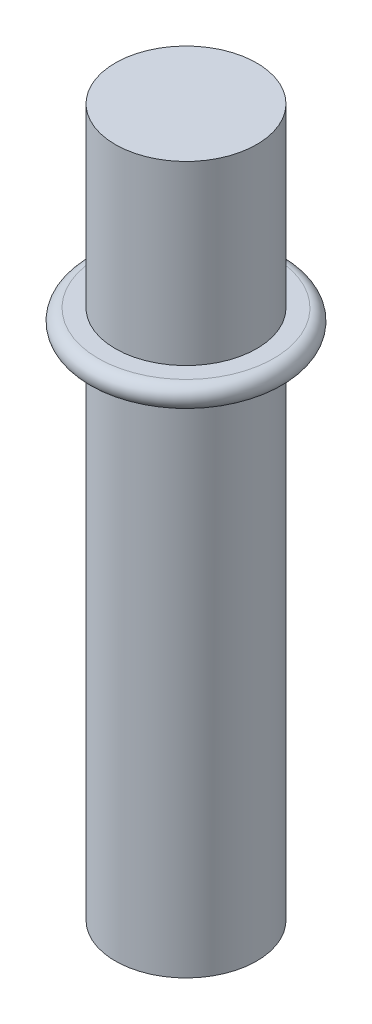
SolidWorks part; units mm, degrees
material "Cast Carbon Steel"
ref_plane "Front Plane" through (0, 0, 0) normal (0, 0, 1) x (1, 0, 0)
ref_plane "Top Plane" through (0, 0, 0) normal (0, 1, 0) x (1, 0, 0)
ref_plane "Right Plane" through (0, 0, 0) normal (1, 0, 0) x (0, 0, -1)
sketch "Sketch2" plane through (0, 0, 0) normal (0, 1, 0) x (1, 0, 0)
  circle A0 centre (0, 0) radius 3.175
  dimension "D1" = 6.35
extrude "Boss-Extrude1" add sketch "Sketch2" along normal blind 14.859
sketch "Sketch3" plane through (0, 14.859, 0) normal (0, 1, 0) x (1, 0, 0)
  circle A0 centre (0, 0) radius 4.445
  dimension "D1" = 8.89
extrude "Boss-Extrude2" add sketch "Sketch3" along normal blind 1.016 separate body
fillet "Fillet2" 2 edges at (0, 15.875, 4.445) (0, 14.859, 4.445) type full round first side face at (0, 15.875, 4.445) second side face at (0, 14.859, 4.445) middle face at (0, 15.875, 4.445)
sketch "Sketch4" plane through (0, 15.875, 0) normal (0, 1, 0) x (1, 0, 0)
  circle A0 centre (0, 0) radius 3.175
  dimension "D1" = 6.35
extrude "Boss-Extrude3" add sketch "Sketch4" along normal blind 7.9375
sketch "Sketch5" plane through (0, 0, 0) normal (0, -1, 0) x (1, 0, 0)
  circle A0 centre (0, 0) radius 3.175
extrude "Boss-Extrude4" add sketch "Sketch5" along normal blind 7.9375
